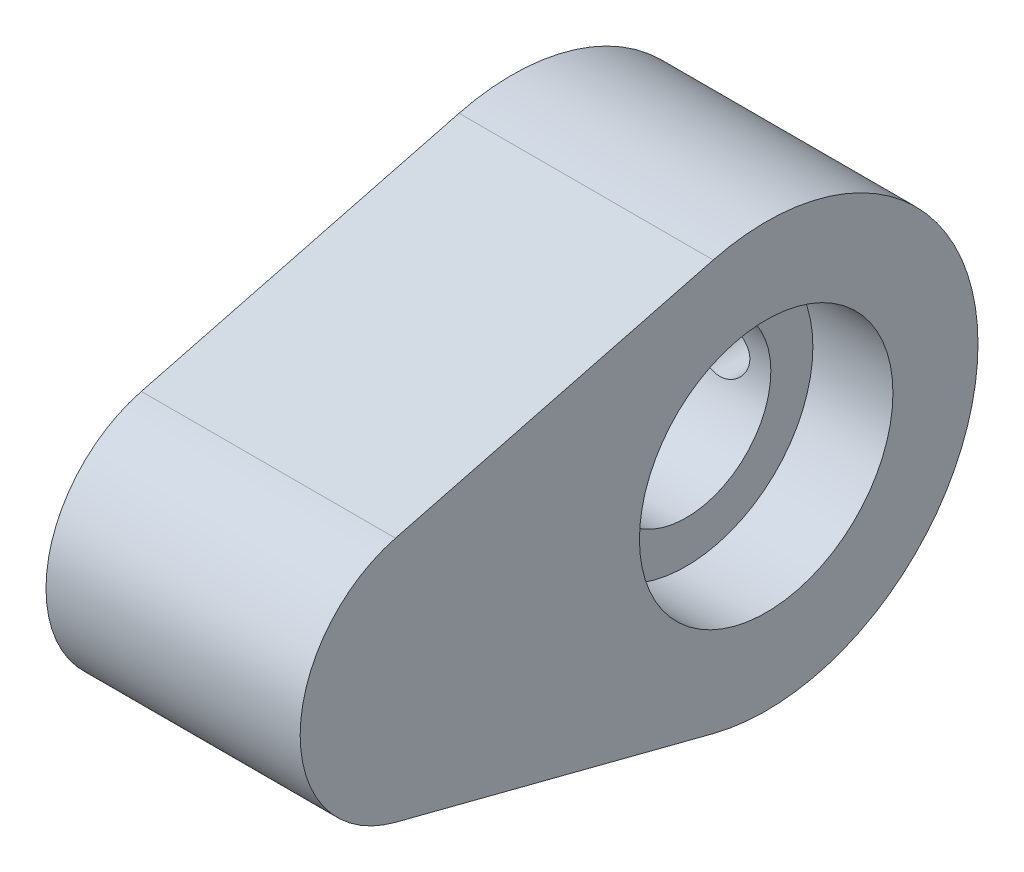
SolidWorks part; units mm, degrees
ref_plane "Front Plane" through (0, 0, 0) normal (0, 0, 1) x (1, 0, 0)
ref_plane "Top Plane" through (0, 0, 0) normal (0, 1, 0) x (1, 0, 0)
ref_plane "Right Plane" through (0, 0, 0) normal (1, 0, 0) x (0, 0, -1)
sketch "Sketch1" plane through (0, 0, 0) normal (1, 0, 0) x (0, 0, -1)
  circle A0 centre (0, 0) radius 9.5
  circle A1 centre (0, 0) radius 15.875
  circle A2 centre (0, 0) radius 6.35
  dimension "D1" = 19
  dimension "D2" = 31.75
  dimension "D3" = 12.7
extrude "Boss-Extrude1" add sketch "Sketch1" along normal blind 6 contours A1 A0 region at (0, 0, 15.426)
extrude "Boss-Extrude2" add sketch "Sketch1<3>" against normal blind 13.05 contours A0 A2 | A1 A0 region at (0, 0, 9.2313) region at (0, 0, 15.426)
sketch "Sketch1<3>" plane through (0, 0, 0) normal (1, 0, 0) x (0, 0, -1) same geometry as "Sketch1"
sketch "Sketch2" plane through (-13.05, 0, 0) normal (-1, 0, 0) x (0, 0, 1)
  line L0 (0, 0) -> (11.1567, 0) construction
  circle A0 centre (0, 12.7) radius 1.95
  circle A1 centre (0, 0) radius 15.875
  circle A2 centre (0, 0) radius 15.875
  circle A3 centre (0, -12.7) radius 1.95
  point P6 (0, 0)
  dimension "D2" = 3.9
  dimension "D3" = 12.7
  dimension "D1" = 0
extrude "Cut-Extrude1" cut sketch "Sketch2" against normal blind 10.16 contours A0 | A3 region at (-13.05, 12.7, 0) region at (-13.05, -12.7, 0)
ref_plane "Plane1" through (0, 0, -15.875) normal (0, 0, 1) x (1, 0, 0)
sketch "Sketch3" plane through (0, 0, -15.875) normal (0, 0, 1) x (1, 0, 0)
  line L0 (-3.525, 0) -> (5.8573, 0) construction
  line L1 (-3.525, 0) -> (-3.525, 15.875) construction
  line L2 (6, 15.875) -> (-13.05, 15.875) construction
  circle A0 centre (-3.525, 0) radius 1.95
  dimension "D1" = 3.9
extrude "Cut-Extrude2" cut sketch "Sketch3" along normal up to surface (9.525 mm away) up to face at (-13.05, 0, -6.35)
sketch "Sketch4" plane through (6, 0, 0) normal (1, 0, 0) x (0, 0, -1)
  line L0 (-3.9688, 15.3709) -> (-27.7812, 9.2225)
  line L1 (0, 0) -> (-25.4, 0) construction
  line L2 (-3.9687, -15.3709) -> (-27.7812, -9.2225)
  circle A0 centre (0, 0) radius 15.875 construction
  circle A1 centre (-25.4, 0) radius 9.525
  point P10 (-26.3425, 0)
  circle M6 centre (0, 0) radius 15.875
  dimension "D1" = 25.4
  dimension "D2" = 19.05
extrude "Boss-Extrude3" add sketch "Sketch4" against normal up to surface (19.05 mm away) contours A1 | A1 L2 M6 | A1 L0 M6 region at (6, 9.4467, 16.1969) region at (6, 0, 25.4) region at (6, -9.4467, 16.1969) up to face at (-13.05, 0, -15.875)
